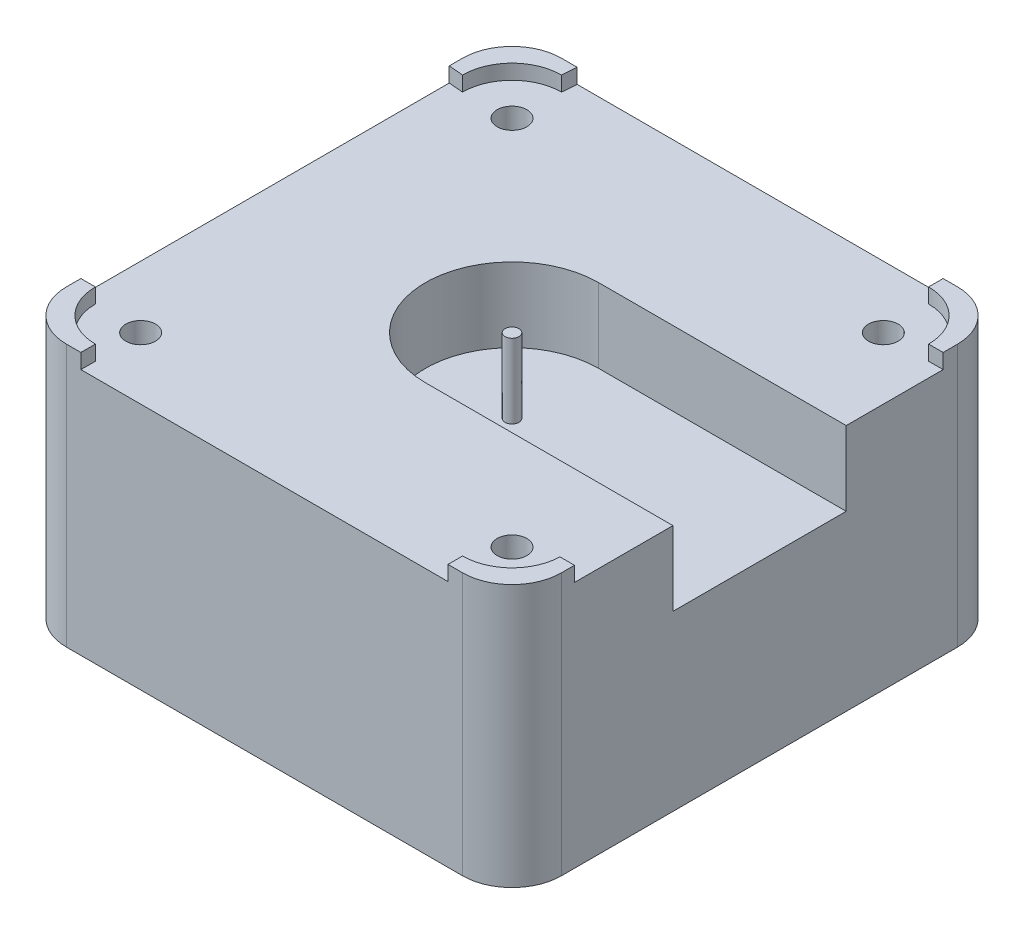
SolidWorks part; units mm, degrees
ref_plane "Front Plane" through (0, 0, 0) normal (0, 0, 1) x (1, 0, 0)
ref_plane "Top Plane" through (0, 0, 0) normal (0, 1, 0) x (1, 0, 0)
ref_plane "Right Plane" through (0, 0, 0) normal (1, 0, 0) x (0, 0, -1)
sketch "Sketch1" plane through (0, 0, 0) normal (0, 1, 0) x (1, 0, 0)
  line L1 (-48.5974, 28.0516) -> (51.4026, 28.0516)
  line L2 (-48.5974, 28.0516) -> (-48.5974, -71.9484)
  line L3 (-48.5974, -71.9484) -> (51.4026, -71.9484)
  line L4 (51.4026, 28.0516) -> (51.4026, -71.9484)
  dimension "D1" = 100
  dimension "D2" = 100
extrude "Boss-Extrude1" add sketch "Sketch1" along normal blind 50
sketch "Sketch2" plane through (0, 50, 0) normal (0, 1, 0) x (1, 0, 0)
  line L0 (1.4026, 28.0516) -> (1.4026, -71.9484) construction
  line L1 (51.4026, 28.0516) -> (-48.5974, 28.0516) construction
  line L2 (-48.5974, -71.9484) -> (51.4026, -71.9484) construction
  line L3 (51.4026, -71.9484) -> (51.4026, 28.0516) construction
  line L4 (-48.5974, -21.9484) -> (51.4026, -21.9484) construction
  line L5 (-48.5974, 28.0516) -> (-48.5974, -71.9484) construction
  line L6 (1.4026, -21.9484) -> (51.4026, -21.9484) construction
  line L7 (1.4026, -4.4484) -> (51.4026, -4.4484)
  line L8 (1.4026, -39.4484) -> (51.4026, -39.4484)
  arc A0 (1.4026, -4.4484) -> (1.4026, -39.4484) centre (1.4026, -21.9484) ccw
  arc A1 (51.4026, -39.4484) -> (51.4026, -4.4484) centre (51.4026, -21.9484) ccw
  point P13 (26.4026, -21.9484)
  dimension "D1" = 50
  dimension "D2" = 50
extrude "Cut-Extrude1" cut sketch "Sketch2" against normal blind 12
sketch "Sketch3" plane through (0, 38, 0) normal (0, 1, 0) x (1, 0, 0)
  line L0 (51.4026, -39.4484) -> (51.4026, -4.4484) construction
  line L1 (51.4026, -4.4484) -> (1.4026, -4.4484) construction
  circle A0 centre (1.4026, -21.9484) radius 1.4
  dimension "D1" = 50
  dimension "D3" = 2.8
  dimension "D2" = 17.5
sketch "Sketch4" plane through (0, 50, 0) normal (0, 1, 0) x (1, 0, 0)
  line L0 (51.4026, -4.4484) -> (51.4026, 28.0516) construction
  line L1 (51.4026, 28.0516) -> (-48.5974, 28.0516) construction
  circle A0 centre (38.9026, 15.5516) radius 3
  circle A1 centre (-36.0974, 15.5516) radius 3
  circle A2 centre (-36.0974, -59.4484) radius 3
  circle A3 centre (38.9026, -59.4484) radius 3
  dimension "D1" = 12.5
  dimension "D2" = 12.5
  dimension "D3" = 2
  dimension "D4" = 2
extrude "Cut-Extrude2" cut sketch "Sketch4" against normal blind 100
sketch "Sketch5" plane through (0, 50, 0) normal (0, 1, 0) x (1, 0, 0)
  line L0 (-48.5974, -61.9484) -> (-48.5974, -71.9484)
  line L5 (-48.5974, 28.0516) -> (-38.5974, 28.0516)
  line L6 (-48.5974, 28.0516) -> (-48.5974, 18.0516)
  line L7 (-48.5974, -71.9484) -> (-38.5974, -71.9484)
  line L8 (51.4026, 28.0516) -> (51.4026, 18.0516)
  line L9 (41.4026, 28.0516) -> (51.4026, 28.0516)
  line L10 (51.4026, -61.9484) -> (51.4026, -71.9484)
  line L11 (41.4026, -71.9484) -> (51.4026, -71.9484)
  arc A0 (-48.5974, -61.9484) -> (-38.5974, -71.9484) centre (-38.5974, -61.9484) ccw
  arc A1 (41.4026, -71.9484) -> (51.4026, -61.9484) centre (41.4026, -61.9484) ccw
  arc A2 (41.4026, 28.0516) -> (51.4026, 18.0516) centre (41.4026, 18.0516) cw
  arc A3 (-38.5974, 28.0516) -> (-48.5974, 18.0516) centre (-38.5974, 18.0516) ccw
  point P10 (51.4026, -71.9484)
  point P15 (-48.5974, 28.0516)
  dimension "D1" = 10
extrude "Cut-Extrude3" cut sketch "Sketch5" against normal blind 50
sketch "Sketch6" plane through (0, 50, 0) normal (0, 1, 0) x (1, 0, 0)
  line L0 (48.4736, 15.1226) -> (51.4026, 15.1226)
  line L5 (51.4026, -4.4484) -> (51.4026, 18.0516) construction
  line L6 (38.4736, 25.1226) -> (38.4736, 28.0516)
  line L7 (41.4026, 28.0516) -> (-38.5974, 28.0516) construction
  line L8 (48.4689, -59.326) -> (51.4026, -59.326)
  line L9 (51.4026, -61.9484) -> (51.4026, -39.4484) construction
  line L10 (38.4736, -69.0195) -> (38.4736, -71.9484)
  line L11 (-38.5974, -71.9484) -> (41.4026, -71.9484) construction
  line L12 (-45.6685, -59.0195) -> (-48.5974, -59.0195)
  line L13 (-48.5974, 18.0516) -> (-48.5974, -61.9484) construction
  line L14 (-35.6685, -69.0195) -> (-35.6685, -71.9484)
  line L15 (-35.6685, 25.1226) -> (-35.4405, 28.0516)
  line L16 (-45.6685, 15.1226) -> (-48.5974, 15.375)
  line L17 (51.4026, 15.1226) -> (51.4026, 18.0516)
  line L18 (-38.5974, -71.9484) -> (-35.6685, -71.9484)
  line L19 (-48.5974, -61.9484) -> (-48.5974, -59.0195)
  line L20 (-38.5974, 28.0516) -> (41.4026, 28.0516)
  line L21 (51.4026, -61.9484) -> (51.4026, -59.326)
  line L22 (-48.5974, 15.375) -> (-48.5974, 18.0516)
  line L23 (38.4736, -71.9484) -> (41.4026, -71.9484)
  arc A0 (51.4026, 18.0516) -> (41.4026, 28.0516) centre (41.4026, 18.0516) ccw construction
  arc A1 (-48.5974, -61.9484) -> (-38.5974, -71.9484) centre (-38.5974, -61.9484) ccw construction
  arc A2 (-35.6685, 25.1226) -> (-45.6685, 15.1226) centre (-35.6685, 15.1226) ccw
  arc A3 (-35.6685, -69.0195) -> (-45.6685, -59.0195) centre (-35.6685, -59.0195) cw
  arc A4 (48.4736, -59.0195) -> (38.4736, -69.0195) centre (38.4736, -59.0195) cw
  arc A5 (38.4736, 25.1226) -> (48.4736, 15.1226) centre (38.4736, 15.1226) cw
  arc A6 (41.4026, 28.0516) -> (51.4026, 18.0516) centre (41.4026, 18.0516) cw
  arc A7 (41.4026, -71.9484) -> (51.4026, -61.9484) centre (41.4026, -61.9484) ccw
  arc A8 (-38.5974, -71.9484) -> (-48.5974, -61.9484) centre (-38.5974, -61.9484) cw
  arc A9 (-48.5974, 18.0516) -> (-38.5974, 28.0516) centre (-38.5974, 18.0516) cw
  point P14 (-45.6685, -69.0195)
  point P19 (48.4736, 25.1226)
  point P45 (51.4026, 28.0516)
  point P50 (-48.5974, -71.9484)
  point P53 (-48.5974, 28.0516)
  dimension "D1" = 10
  dimension "D4" = 10
  dimension "D2" = 100
  dimension "D3" = 0
extrude "Boss-Extrude4" add sketch "Sketch6" along normal blind 3 contours L6 A5 L0 L13 L14 L15 | L8 A4 L10 L7 L9 | A2 L15 L0 L5 L16 | L14 A3 L12 L5 L6 L7 region at (46.1828, 50, -22.8318) region at (-43.3777, 50, 66.7287) region at (-43.3156, 50, -22.8949) region at (46.1319, 50, 66.8311)
extrude "Cut-Extrude4" cut sketch "Sketch2<2>" against normal blind 15
sketch "Sketch2<2>" plane through (0, 50, 0) normal (0, 1, 0) x (1, 0, 0) same geometry as "Sketch2"
sketch "Sketch7" plane through (0, 35, 0) normal (0, 1, 0) x (1, 0, 0)
  line L0 (1.4026, -39.4484) -> (51.4026, -39.4484) construction
  line L1 (51.4026, -39.4484) -> (51.4026, -4.4484) construction
  circle A0 centre (1.4026, -21.9484) radius 1.4
  dimension "D1" = 17.5
  dimension "D2" = 50
extrude "Boss-Extrude5" add sketch "Sketch7" along normal blind 15
